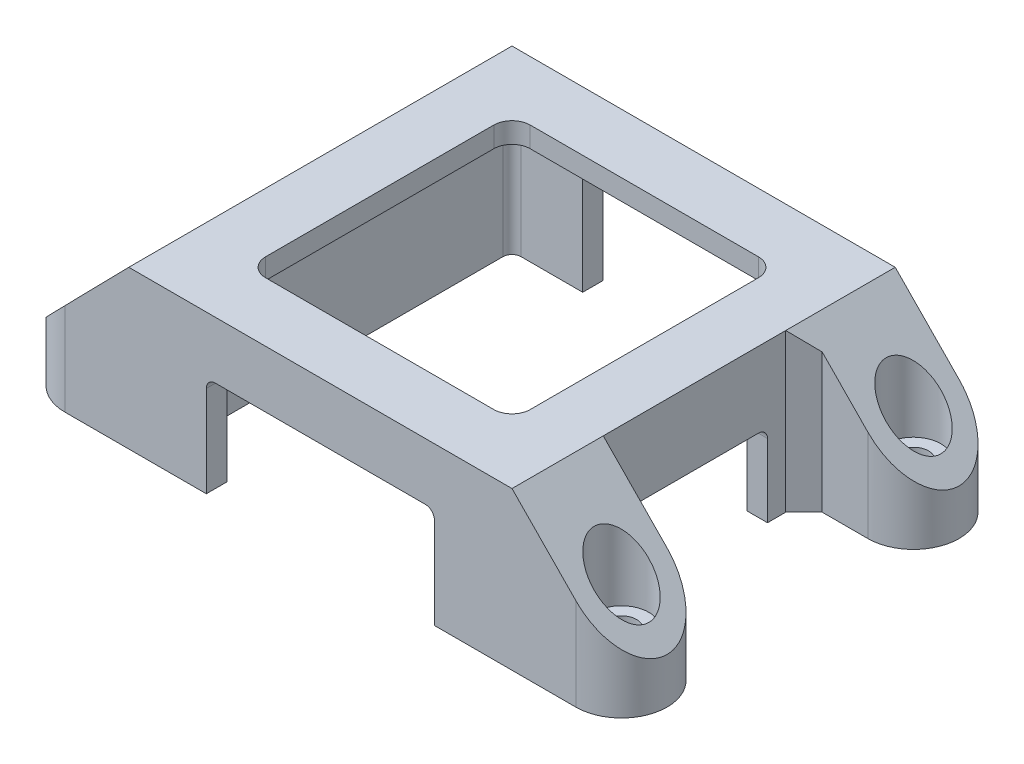
SolidWorks part; units mm, degrees
ref_plane "Front Plane" through (0, 0, 0) normal (0, 0, 1) x (1, 0, 0)
ref_plane "Top Plane" through (0, 0, 0) normal (0, 1, 0) x (1, 0, 0)
ref_plane "Right Plane" through (0, 0, 0) normal (1, 0, 0) x (0, 0, -1)
sketch "Sketch1" plane through (0, 0, 0) normal (0, 1, 0) x (1, 0, 0)
  line L5 (-18.75, -18.75) -> (18.75, -18.75)
  line L6 (-18.75, -18.75) -> (-18.75, 18.75)
  line L7 (-18.75, 18.75) -> (18.75, 18.75)
  line L8 (18.75, -18.75) -> (18.75, 18.75)
  line L9 (-18.75, -18.75) -> (18.75, 18.75) construction
  line L10 (-18.75, 18.75) -> (18.75, -18.75) construction
  point P0 (0, 0)
  dimension "D1" = 37.5
extrude "Boss-Extrude1" add sketch "Sketch1" along normal blind 15
shell "Shell1" thickness 2.25 removed face at (0, 0, 0) outward yes
sketch "Sketch2" plane through (0, 0, 21) normal (0, 0, 1) x (1, 0, 0)
  line L1 (-12.5, 0) -> (12.5, 0)
  line L2 (-12.5, 0) -> (-12.5, 11)
  line L3 (-12.5, 11) -> (12.5, 11)
  line L4 (12.5, 0) -> (12.5, 11)
  line L5 (-12.5, 11) -> (12.5, 0) construction
  line L6 (-21, 0) -> (21, 0) construction
  point P6 (0, 5.5)
  dimension "D1" = 11
  dimension "D2" = 25
extrude "Cut-Extrude1" cut sketch "Sketch2" against normal up to next
sketch "Sketch3" plane through (21, 0, 0) normal (1, 0, 0) x (0, 0, -1)
  line L1 (-11, 0) -> (7, 0)
  line L2 (-11, 0) -> (-11, 9)
  line L3 (-11, 9) -> (7, 9)
  line L4 (7, 0) -> (7, 9)
  line L6 (-21, 17.25) -> (-21, 0) construction
  line L7 (-21, 0) -> (21, 0) construction
  dimension "D1" = 18
  dimension "D2" = 9
  dimension "D3" = 10
extrude "Cut-Extrude2" cut sketch "Sketch3" against normal up to next
sketch "Sketch5" plane through (0, 17.25, 0) normal (0, 1, 0) x (1, 0, 0)
  line L5 (-14.5, -14.5) -> (14.5, -14.5)
  line L6 (-14.5, -14.5) -> (-14.5, 14.5)
  line L7 (-14.5, 14.5) -> (14.5, 14.5)
  line L8 (14.5, -14.5) -> (14.5, 14.5)
  line L9 (-14.5, -14.5) -> (14.5, 14.5) construction
  line L10 (-14.5, 14.5) -> (14.5, -14.5) construction
  point P3 (0, 0)
  dimension "D1" = 29
extrude "Cut-Extrude3" cut sketch "Sketch5" against normal up to next
fillet "Fillet1" radius 2 4 edges at (-14.5, 16.125, 14.5) (14.5, 16.125, 14.5) (14.5, 16.125, -14.5) (-14.5, 16.125, -14.5)
sketch "Sketch6" plane through (0, 0, -21) normal (0, 0, -1) x (-1, 0, 0)
  line L1 (-11, 0) -> (11, 0)
  line L2 (-11, 0) -> (-11, 14)
  line L3 (-11, 14) -> (11, 14)
  line L4 (11, 0) -> (11, 14)
  line L5 (-11, 14) -> (11, 0) construction
  line L6 (-21, 0) -> (21, 0) construction
  point P6 (0, 7)
  dimension "D1" = 22
  dimension "D2" = 14
extrude "Cut-Extrude4" cut sketch "Sketch6" against normal up to next
fillet "Fillet2" radius 1 6 edges at (-11, 14, -19.875) (11, 14, -19.875) (19.875, 9, -7) (19.875, 9, 11) (12.5, 11, 19.875) (-12.5, 11, 19.875)
sketch "Sketch9" plane through (0, 0, 0) normal (0, -1, 0) x (1, 0, 0)
  line L1 (-21, 21) -> (-33, 21)
  line L2 (-21, 21) -> (-21, 11)
  line L3 (-21, 11) -> (-33, 11)
  line L4 (-33, 21) -> (-33, 11)
  dimension "D1" = 10
  dimension "D2" = 12
extrude "Boss-Extrude3" add sketch "Sketch9" against normal blind 5
sketch "Sketch10" plane through (0, 0, 21) normal (0, 0, 1) x (1, 0, 0)
  line L0 (-21, 17.25) -> (-33, 5)
  line L1 (-33, 5) -> (-21, 5)
  line L2 (-21, 5) -> (-21, 17.25)
extrude "Boss-Extrude4" add sketch "Sketch10" against normal up to surface (10 mm away) up to face at (-27, 2.5, 11)
sketch "Sketch11" plane through (0, 0, 0) normal (0, -1, 0) x (1, 0, 0)
  line L0 (-33, 21) -> (-33, 11) construction
  line L1 (-33, 21) -> (-12.5, 21) construction
  circle A0 centre (-28, 16) radius 1.65
  point P4 (-33, 16)
  dimension "D1" = 3.3
  dimension "D2" = 5
  dimension "D3" = 5
extrude "Cut-Extrude5" cut sketch "Sketch11" against normal blind 5
sketch "Sketch12" plane through (0, 5, 0) normal (0, -1, 0) x (1, 0, 0)
  circle A0 centre (-28, 16) radius 3
  dimension "D1" = 6
extrude "Cut-Extrude6" cut sketch "Sketch12" against normal up to next contours A0
sketch "Sketch13" plane through (0, 0, 0) normal (0, -1, 0) x (1, 0, 0)
  circle A0 centre (-28, 16) radius 5
  line M8 (-12.5, 21) -> (-33, 21)
  line M9 (-33, 21) -> (-33, 11)
  line M10 (-33, 11) -> (-21, 11)
  dimension "D1" = 10
extrude "Cut-Extrude7" cut sketch "Sketch13" against normal up to next contours A0 M8 M9 | A0 M9 M10 region at (-31.8832, 0, 19.8832) region at (-31.8832, 0, 12.1168)
mirror "Mirror1" about plane through (0, 0, 0) normal (0, 0, 1) of "Boss-Extrude4", "Boss-Extrude3", "Cut-Extrude7", "Cut-Extrude6", "Cut-Extrude5"
mirror "Mirror3" about plane through (0, 0, 0) normal (1, 0, 0) of "Mirror1"
chamfer "Chamfer1" distance 2 angle 45 3 edges at (21, 8.625, -11) (-21, 8.625, 11) (-21, 8.625, -11)
fillet "Fillet3" radius 1 4 edges at (18.75, 7.5, -18.75) (-18.75, 7.5, 18.75) (18.75, 7.5, 18.75) (-18.75, 7.5, -18.75)
